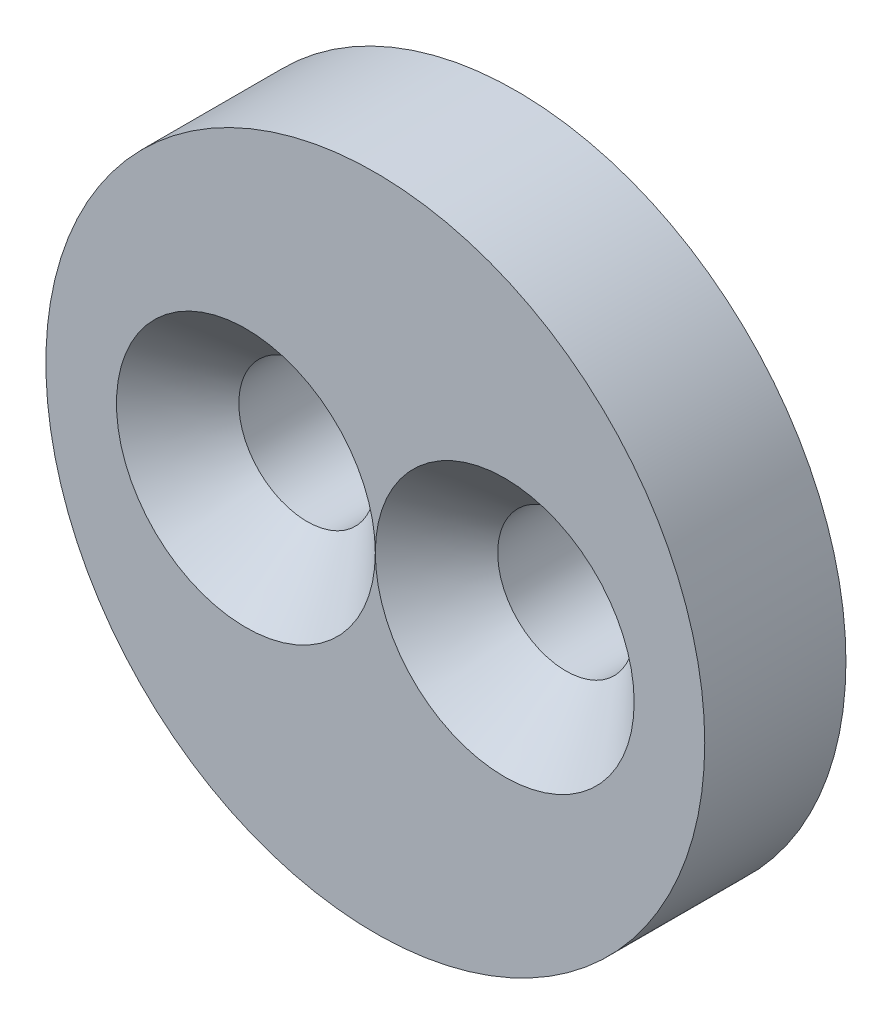
SolidWorks part; units mm, degrees
ref_plane "Front Plane" through (0, 0, 0) normal (0, 0, 1) x (1, 0, 0)
ref_plane "Top Plane" through (0, 0, 0) normal (0, 1, 0) x (1, 0, 0)
ref_plane "Right Plane" through (0, 0, 0) normal (1, 0, 0) x (0, 0, -1)
sketch "Sketch1" plane through (0, 0, 27.3) normal (0, 0, 1) x (1, 0, 0)
  circle A0 centre (0, 0) radius 7
  circle A1 centre (0, 0) radius 7.4923 construction
  dimension "D1" = 14
extrude "Boss-Extrude1" add sketch "Sketch1" along normal blind 3
hole_wizard "CSK for M2.5 Countersunk Flat Head Screw1" positions "Sketch2" profile "Sketch4" countersink size "M2.5" standard "ISO" end condition through all
sketch "Sketch2" plane through (0, 0, 30.3) normal (0, 0, 1) x (1, 0, 0)
  point P0 (-2.75, 0)
  point P3 (2.75, 0)
sketch "Sketch4" plane through (-2.75, 0, 30.3) normal (1, 0, 0) x (0, -1, 0)
  line L0 (0, 0) -> (0, 3)
  line L1 (0, 3) -> (1.45, 3)
  line L2 (1.45, 3) -> (1.45, 1.3)
  line L3 (1.45, 1.3) -> (2.75, 0)
  line L5 (2.75, 0) -> (0, 0)
  line L6 (-1.45, 1.3) -> (-2.75, 0) construction
  line L11 (0, -6.35) -> (0, 107.95) construction
  dimension "Thru Hole Dia." = 2.9
  dimension "Thru Hole Depth" = 3
  dimension "Near C'Sink Dia." = 5.5
  dimension "Near C'Sink Angle" = 90
